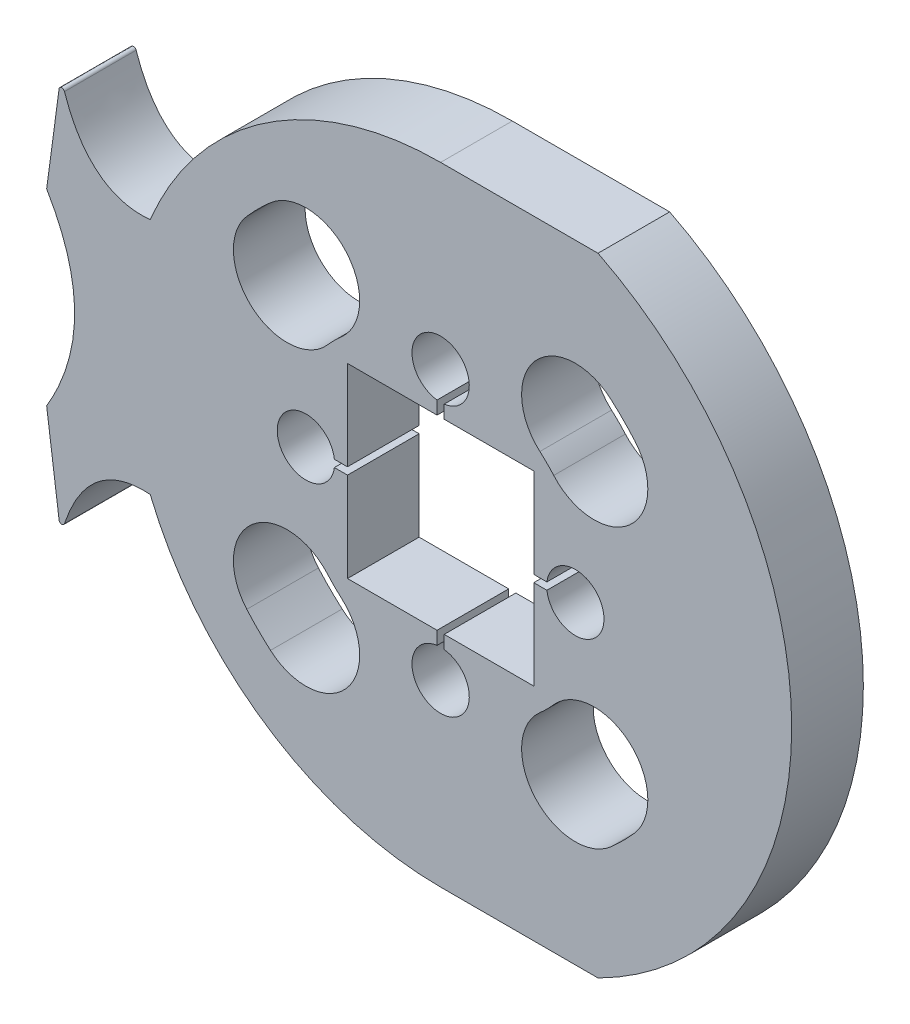
SolidWorks part; units mm, degrees
material "AISI 1020 Steel, Cold Rolled"
ref_plane "Front Plane" through (0, 0, 0) normal (0, 0, 1) x (1, 0, 0)
ref_plane "Top Plane" through (0, 0, 0) normal (0, 1, 0) x (1, 0, 0)
ref_plane "Right Plane" through (0, 0, 0) normal (1, 0, 0) x (0, 0, -1)
other "Center of Mass"
sketch "Sketch1" plane through (0, 0, 0) normal (0, 0, 1) x (1, 0, 0)
  line L0 (-11.938, 0) -> (0, 0) construction
  line L1 (-8.255, 8.255) -> (8.255, 8.255)
  line L2 (-8.255, 8.255) -> (-8.255, -8.255)
  line L3 (-8.255, -8.255) -> (8.255, -8.255)
  line L4 (8.255, 8.255) -> (8.255, -8.255)
  line L5 (0, 0) -> (0, 11.938) construction
  line L6 (11.938, 0) -> (0, 0) construction
  line L7 (0, 0) -> (0, -11.938) construction
  line L9 (-9.4179, 0.3175) -> (9.4179, 0.3175)
  line L10 (-9.4179, 0.3175) -> (-9.4179, -0.3175)
  line L11 (-9.4179, -0.3175) -> (9.4179, -0.3175)
  line L12 (9.4179, 0.3175) -> (9.4179, -0.3175)
  line L13 (-0.3175, 9.4179) -> (0.3175, 9.4179)
  line L14 (-0.3175, 9.4179) -> (-0.3175, -9.4179)
  line L15 (-0.3175, -9.4179) -> (0.3175, -9.4179)
  line L16 (0.3175, 9.4179) -> (0.3175, -9.4179)
  line L17 (0, 27.813) -> (13.9492, 27.813)
  line L18 (0, -27.813) -> (13.9492, -27.813)
  line L19 (-33.8048, 16.6086) -> (-34.9172, 8.3198)
  line L20 (-34.9172, -8.3198) -> (-33.8048, -16.6086)
  arc A0 (8.7964, -10.0222) -> (10.0222, -8.7964) centre (0, 0) ccw
  circle A1 centre (0, 11.938) radius 2.54
  circle A2 centre (0, -11.938) radius 2.54
  circle A3 centre (11.938, 0) radius 2.54
  circle A4 centre (-11.938, 0) radius 2.54
  arc A5 (15.0796, -17.181) -> (17.181, -15.0796) centre (0, 0) ccw
  arc A7 (-17.181, 15.0796) -> (-10.0222, 8.7964) centre (-13.6016, 11.938) ccw
  arc A8 (-10.0222, -8.7964) -> (-17.181, -15.0796) centre (-13.6016, -11.938) ccw
  arc A10 (-8.7964, 10.0222) -> (-15.0796, 17.181) centre (-11.938, 13.6016) ccw
  arc A11 (17.181, -15.0796) -> (10.0222, -8.7964) centre (13.6016, -11.938) ccw
  arc A13 (-15.0796, -17.181) -> (-8.7964, -10.0222) centre (-11.938, -13.6016) ccw
  arc A14 (8.7964, -10.0222) -> (15.0796, -17.181) centre (11.938, -13.6016) ccw
  arc A15 (-10.0222, -8.7964) -> (-8.7964, -10.0222) centre (0, 0) ccw
  arc A16 (-17.181, -15.0796) -> (-15.0796, -17.181) centre (0, 0) ccw
  arc A19 (-8.7964, 10.0222) -> (-10.0222, 8.7964) centre (0, 0) ccw
  arc A20 (-15.0796, 17.181) -> (-17.181, 15.0796) centre (0, 0) ccw
  arc A23 (10.0222, 8.7964) -> (17.181, 15.0796) centre (13.6016, 11.938) ccw [skipped]
  arc A24 (15.0796, 17.181) -> (8.7964, 10.0222) centre (11.938, 13.6016) ccw [skipped]
  arc A25 (-8.7964, 10.0222) -> (-15.0796, 17.181) centre (-11.938, 13.6016) ccw
  arc A26 (-17.181, 15.0796) -> (-10.0222, 8.7964) centre (-13.6016, 11.938) ccw
  arc A27 (-15.0796, 17.181) -> (-17.181, 15.0796) centre (0, 0) ccw
  arc A28 (10.0222, 8.7964) -> (17.181, 15.0796) centre (13.6016, 11.938) ccw
  arc A29 (15.0796, 17.181) -> (8.7964, 10.0222) centre (11.938, 13.6016) ccw
  arc A30 (17.181, 15.0796) -> (15.0796, 17.181) centre (0, 0) ccw
  arc A31 (8.7964, -10.0222) -> (15.0796, -17.181) centre (11.938, -13.6016) ccw
  arc A32 (17.181, -15.0796) -> (10.0222, -8.7964) centre (13.6016, -11.938) ccw
  arc A33 (15.0796, -17.181) -> (17.181, -15.0796) centre (0, 0) ccw
  arc A34 (-8.7964, 10.0222) -> (-10.0222, 8.7964) centre (0, 0) ccw
  arc A35 (10.0222, 8.7964) -> (8.7964, 10.0222) centre (0, 0) ccw
  arc A36 (8.7964, -10.0222) -> (10.0222, -8.7964) centre (0, 0) ccw
  arc A37 (-25.7359, -10.5464) -> (0, -27.813) centre (0, 0) ccw
  arc A39 (-33.3353, 16.5776) -> (-33.8048, 16.6086) centre (-33.5763, 16.4976) ccw
  arc A40 (-33.3353, -16.5776) -> (-33.8048, -16.6086) centre (-33.5763, -16.4976) cw
  arc A41 (13.9492, -27.813) -> (13.9492, 27.813) centre (0, 0) ccw
  arc A42 (0, 27.813) -> (-25.7359, 10.5464) centre (0, 0) ccw
  spline S0 degree 3 poles (-33.3353, 16.5776) (-31.8977, 12.2441) (-29.218, 10.1877) (-25.7359, 10.5464) knots 0.081541 0.081541 0.081541 0.081541 1 1 1 1
  spline S1 degree 3 poles (-33.3353, -16.5776) (-31.8977, -12.2441) (-29.2304, -10.2896) (-25.7359, -10.5464) knots 0.081541 0.081541 0.081541 0.081541 1 1 1 1
  spline S2 degree 2 poles (-34.9172, 8.3198) (-29.9564, 0) (-34.9172, -8.3198) knots 0 0 0 1 1 1
  point P7 (8.255, 0)
  point P8 (0, 8.255)
  point P54 (0, 0)
  point P70 (0, 0)
  point P77 (0, 0)
  dimension "D2" = 26.67
  dimension "D4" = 5.08
  dimension "D6" = 45.72
  dimension "D7" = 4
  dimension "D10" = 55.626
  dimension "D12" = 0.254
  dimension "D14" = 62.23
  dimension "D1" = 16.51
  dimension "D3" = 11.938
  dimension "D5" = 0.635
  dimension "D9" = 4
  dimension "D8" = 4
extrude "Boss-Extrude1" add sketch "Sketch1" along normal blind 6.35 contours A0 A4 L9 L2 L1 L14 A1 L16 L4 A3 L11 L3 A2 region at (6.9746, 26.9496, 0)
